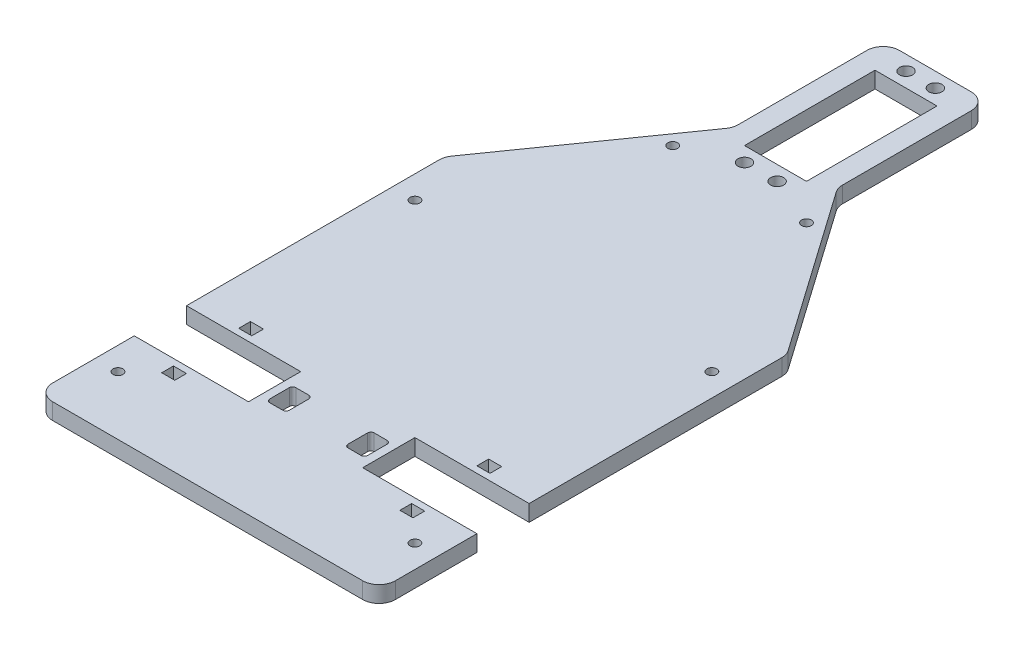
SolidWorks part; units mm, degrees
ref_plane "Front Plane" through (0, 0, 0) normal (0, 0, 1) x (1, 0, 0)
ref_plane "Top Plane" through (0, 0, 0) normal (0, 1, 0) x (1, 0, 0)
ref_plane "Right Plane" through (0, 0, 0) normal (1, 0, 0) x (0, 0, -1)
sketch "Sketch1" plane through (0, 0, 0) normal (0, 1, 0) x (1, 0, 0)
  line L0 (-16, 108) -> (16, 108)
  line L1 (16, 108) -> (16, 62)
  line L2 (16, 62) -> (52.5, 10)
  line L3 (52.5, 10) -> (52.5, -115)
  line L4 (52.5, -115) -> (-52.5, -115)
  line L5 (-52.5, -115) -> (-52.5, 10)
  line L6 (-52.5, 10) -> (-16, 62)
  line L7 (-16, 62) -> (-16, 108)
  dimension "D1" = 52.5
  dimension "D2" = 105
  dimension "D3" = 16
  dimension "D4" = 32
  dimension "D5" = 125
  dimension "D6" = 108
  dimension "D7" = 125
  dimension "D8" = 46
  dimension "D9" = 52
  dimension "D10" = 52
extrude "Boss-Extrude1" add sketch "Sketch1" along normal blind 5
sketch "Sketch2" plane through (0, 5, 0) normal (0, 1, 0) x (1, 0, 0)
  line L5 (-9.5, 59) -> (-9.5, 99)
  line L6 (-52.5, 10) -> (-52.5, -115) construction
  line L10 (-38.5, -63.4024) -> (-34.5042, -63.4024)
  line L11 (-38.5, -63.4024) -> (-38.5, -67)
  line L16 (52.5, 10) -> (52.5, -115) construction
  line L17 (-52.5, -69) -> (-17.5, -69)
  line L18 (-52.5, -115) -> (-52.5, 10) construction
  line L19 (-17.5, -69) -> (-17.5, -85)
  line L20 (-17.5, -85) -> (-52.5, -85)
  line L21 (-52.5, -85) -> (-52.5, -69)
  line L22 (17.5, -85) -> (17.5, -69)
  line L23 (17.5, -85) -> (52.5, -85)
  line L24 (17.5, -69) -> (52.5, -69)
  line L25 (52.5, -69) -> (52.5, -85)
  line L26 (-38.5, -67) -> (-34.5042, -67)
  line L27 (52.5, -115) -> (-52.5, -115) construction
  line L29 (-15, -82) -> (-9, -82)
  line L30 (-9, -82) -> (-9, -74)
  line L31 (-15, -74) -> (-9, -74)
  line L32 (-15, -82) -> (-15, -74)
  line L33 (9, -74) -> (9, -82)
  line L34 (9, -82) -> (15, -82)
  line L35 (15, -82) -> (15, -74)
  line L36 (15, -74) -> (9, -74)
  line L37 (-16, 108) -> (16, 108) construction
  line L38 (-16, 62) -> (-16, 108) construction
  line L39 (-34.5042, -63.4024) -> (-34.5042, -67)
  line L40 (-9.5, 99) -> (9.5, 99)
  line L41 (9.5, 99) -> (9.5, 59)
  line L42 (9.5, 59) -> (-9.5, 59)
  line L43 (-38.5, -87) -> (-34.5042, -87)
  line L44 (-38.5, -87) -> (-38.5, -90.6)
  line L45 (-38.5, -90.6) -> (-34.5042, -90.6)
  line L46 (-34.5042, -87) -> (-34.5042, -90.6)
  line L48 (34.5, -87) -> (38.5, -87)
  line L49 (34.5, -87) -> (34.5, -90.6)
  line L50 (34.5, -90.6) -> (38.5, -90.6)
  line L51 (38.5, -87) -> (38.5, -90.6)
  line L52 (34.5, -63.4) -> (38.5, -63.4)
  line L53 (34.5, -63.4) -> (34.5, -67)
  line L54 (34.5, -67) -> (38.5, -67)
  line L55 (38.5, -63.4) -> (38.5, -67)
  circle A0 centre (-4.5, 103.5) radius 2
  circle A1 centre (4.5, 103.5) radius 2
  circle A2 centre (-5, 54.5026) radius 2
  circle A3 centre (5, 54.5026) radius 2
  circle A6 centre (-20.5, 48) radius 1.5
  circle A7 centre (20.5, 48) radius 1.5
  circle A8 centre (45.5, -6) radius 1.5
  circle A9 centre (-45.5, -6) radius 1.5
  circle A10 centre (45.5, -97) radius 1.5
  circle A11 centre (-45.5, -97) radius 1.5
  point P20 (-38.5, -65.2012)
  point P73 (38.5, -65.2)
  dimension "D5" = 4
  dimension "D8" = 4
  dimension "D11" = 4
  dimension "D14" = 40
  dimension "D21" = 91
  dimension "D24" = 16
  dimension "D27" = 3
  dimension "D30" = 3
  dimension "D37" = 3
  dimension "D38" = 3
  dimension "D39" = 3
  dimension "D40" = 3
  dimension "D46" = 2
  dimension "D26" = 4
  dimension "D7" = 4.5
  dimension "D9" = 19
  dimension "D10" = 4.5
  dimension "D12" = 6.5
  dimension "D13" = 11
  dimension "D15" = 49
  dimension "D16" = 49
  dimension "D17" = 11
  dimension "D18" = 60
  dimension "D19" = 60
  dimension "D20" = 7
  dimension "D22" = 91
  dimension "D23" = 32
  dimension "D25" = 16
  dimension "D28" = 32
  dimension "D29" = 3.9958
  dimension "D31" = 3.5976
  dimension "D32" = 2
  dimension "D33" = 7
  dimension "D34" = 14
  dimension "D35" = 7
  dimension "D36" = 14
  dimension "D41" = 7
  dimension "D42" = 4.5
  dimension "D43" = 3.9958
  dimension "D44" = 5
  dimension "D45" = 5
  dimension "D47" = 3.6
  dimension "D48" = 3.6
  dimension "D49" = 35
  dimension "D50" = 16
  dimension "D51" = 30
  dimension "D52" = 16
  dimension "D53" = 35
  dimension "D54" = 30
  dimension "D55" = 8
  dimension "D56" = 6
  dimension "D57" = 2.5
  dimension "D58" = 5
  dimension "D59" = 8
  dimension "D60" = 6
  dimension "D61" = 2.5
  dimension "D62" = 5
  dimension "D63" = 4
  dimension "D64" = 2
  dimension "D65" = 14
  dimension "D66" = 14
  dimension "D67" = 4
  dimension "D68" = 3.6
  dimension "D69" = 2
extrude "Cut-Extrude1" cut sketch "Sketch2" against normal blind 7
fillet "Fillet1" radius 5 1 edges at (16, 2.5, -108)
fillet "Fillet2" radius 5 1 edges at (-16, 2.5, -108)
fillet "Fillet3" radius 5 1 edges at (52.5, 2.5, -10)
fillet "Fillet4" radius 5 1 edges at (-52.5, 2.5, -10)
fillet "Fillet5" radius 5 1 edges at (52.5, 2.5, 115)
fillet "Fillet6" radius 5 1 edges at (-52.5, 2.5, 115)
fillet "Fillet8" radius 1 1 edges at (15, 2.5, 74)
fillet "Fillet9" radius 1 7 edges at (-15, 2.5, 82) (-15, 2.5, 74) (-9, 2.5, 82) (-9, 2.5, 74) (9, 2.5, 82) (15, 2.5, 82) (9, 2.5, 74)
fillet "Fillet10" radius 5 2 edges at (-16, 2.5, -62) (16, 2.5, -62)
